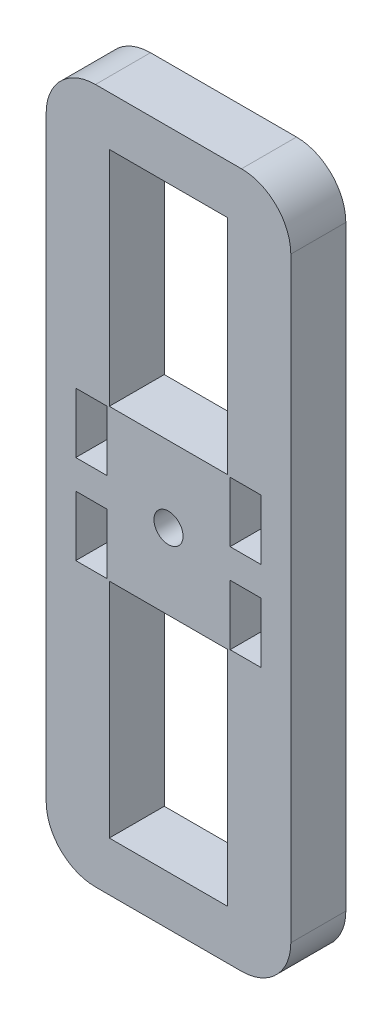
SolidWorks part; units mm, degrees
material "Acrylic (Medium-high impact)"
ref_plane "Front Plane" through (0, 0, 0) normal (0, 0, 1) x (1, 0, 0)
ref_plane "Top Plane" through (0, 0, 0) normal (0, 1, 0) x (1, 0, 0)
ref_plane "Right Plane" through (0, 0, 0) normal (1, 0, 0) x (0, 0, -1)
sketch "Sketch1" plane through (0, 0, 0) normal (0, 0, 1) x (1, 0, 0)
  line L0 (709.6907, 498.1997) -> (721.7007, 498.1997)
  line L1 (721.7007, 498.1997) -> (721.7007, 475.6297)
  line L2 (721.7007, 475.6297) -> (709.6907, 475.6297)
  line L3 (709.6907, 475.6297) -> (709.6907, 498.1997)
  line L4 (715.6957, 432.7097) -> (723.1007, 432.7097)
  line L5 (715.6957, 503.1997) -> (708.2907, 503.1997)
  line L6 (715.6957, 503.1997) -> (723.1007, 503.1997)
  line L7 (715.6957, 460.2797) -> (715.6957, 475.6297) construction
  line L8 (709.6907, 498.1997) -> (703.2907, 498.1997) construction
  line L9 (721.7007, 498.1997) -> (728.1007, 498.1997) construction
  line L10 (709.4457, 475.5297) -> (706.2907, 475.5297)
  line L11 (728.1007, 498.1997) -> (728.1007, 437.7097)
  line L12 (709.4457, 475.5297) -> (709.4457, 469.4297)
  line L13 (709.4457, 469.4297) -> (706.2907, 469.4297)
  line L14 (706.2907, 469.4297) -> (706.2907, 475.5297)
  line L15 (703.2907, 498.1997) -> (703.2907, 437.7097)
  line L16 (721.9457, 475.5297) -> (725.1007, 475.5297)
  line L17 (725.1007, 469.4297) -> (725.1007, 475.5297)
  line L18 (721.9457, 469.4297) -> (725.1007, 469.4297)
  line L19 (721.9457, 475.5297) -> (721.9457, 469.4297)
  line L20 (721.9457, 460.3797) -> (725.1007, 460.3797)
  line L21 (725.1007, 466.4797) -> (725.1007, 460.3797)
  line L22 (715.6957, 432.7097) -> (708.2907, 432.7097)
  line L23 (721.9457, 469.4297) -> (49717.0384, 469.4297) construction
  line L24 (709.6907, 466.4797) -> (715.6957, 466.4797) construction
  line L25 (725.1007, 466.4797) -> (49717.0384, 466.4797) construction
  line L26 (709.4457, 460.3797) -> (706.2907, 460.3797)
  line L27 (706.2907, 466.4797) -> (706.2907, 460.3797)
  line L28 (721.9457, 466.4797) -> (725.1007, 466.4797)
  line L29 (721.9457, 460.3797) -> (721.9457, 466.4797)
  line L30 (-282.9616, 469.4297) -> (709.4457, 469.4297) construction
  line L31 (-282.9616, 466.4797) -> (706.2907, 466.4797) construction
  line L32 (709.4457, 466.4797) -> (706.2907, 466.4797)
  line L33 (709.4457, 460.3797) -> (709.4457, 466.4797)
  line L37 (709.6907, 460.2797) -> (709.6907, 437.7097)
  line L38 (721.7007, 460.2797) -> (709.6907, 460.2797)
  line L39 (721.7007, 437.7097) -> (721.7007, 460.2797)
  line L40 (709.6907, 437.7097) -> (721.7007, 437.7097)
  line L171 (-296.4722, 467.9547) -> (49703.5278, 467.9547) construction
  circle A0 centre (715.6957, 467.9547) radius 1.475
  arc A1 (708.2907, 432.7097) -> (703.2907, 437.7097) centre (708.2907, 437.7097) cw
  arc A2 (708.2907, 503.1997) -> (703.2907, 498.1997) centre (708.2907, 498.1997) ccw
  arc A3 (723.1007, 503.1997) -> (728.1007, 498.1997) centre (723.1007, 498.1997) cw
  arc A4 (723.1007, 432.7097) -> (728.1007, 437.7097) centre (723.1007, 437.7097) ccw
  point P6 (715.6957, 504.6992)
  point P33 (715.6957, 475.6297)
  point P37 (715.6957, 467.9547)
  point P46 (715.6957, 431.2102)
  dimension "D1" = 6.1
  dimension "D4" = 2.95
  dimension "D3" = 0.1
  dimension "D5" = 22.57
  dimension "D6" = 12.01
  dimension "D7" = 3
  dimension "D8" = 5
  dimension "D9" = 12.5
extrude "Boss-Extrude1" add sketch "Sketch1" along normal blind 5.58 contours L2 L3 L0 L1 L40 L37 L38 L39 A0 region at (711.9932, 433.457, 0)
